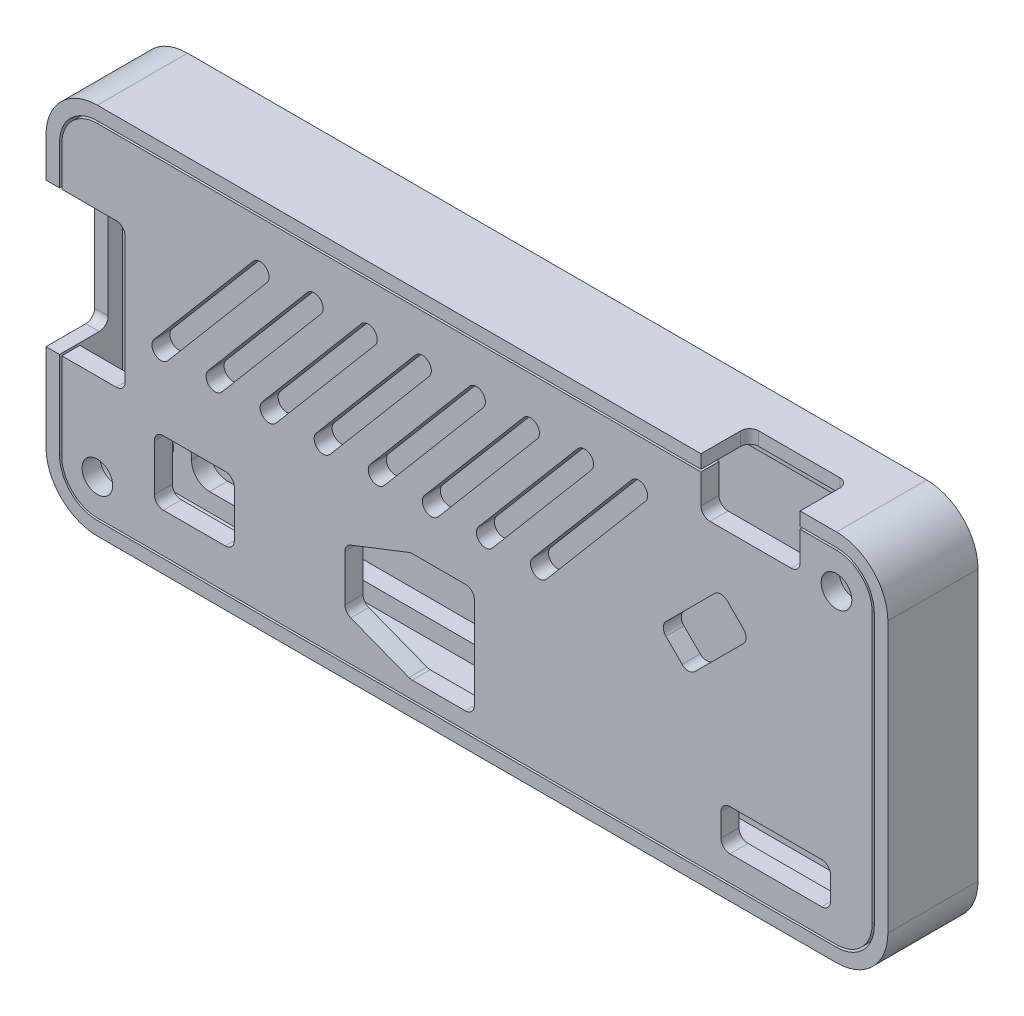
SolidWorks part; units mm, degrees
ref_plane "Front" through (0, 0, 0) normal (0, 0, 1) x (1, 0, 0)
ref_plane "Top" through (0, 0, 0) normal (0, 1, 0) x (1, 0, 0)
ref_plane "Right" through (0, 0, 0) normal (1, 0, 0) x (0, 0, -1)
sketch "Sketch1" plane through (0, 0, 0) normal (0, 0, 1) x (1, 0, 0)
  line L0 (-0.2, 4) -> (-0.2, 34)
  line L1 (4, 0) -> (86, 0) construction
  line L2 (0, 4) -> (0, 34) construction
  line L3 (4, 38) -> (86, 38) construction
  line L4 (90, 4) -> (90, 34) construction
  line L5 (4, 38.2) -> (86, 38.2)
  line L6 (90.2, 4) -> (90.2, 34)
  line L7 (4, -0.2) -> (86, -0.2)
  line L8 (4, 39.7) -> (86, 39.7)
  line L9 (91.7, 4) -> (91.7, 34)
  line L10 (4, -1.7) -> (86, -1.7)
  line L11 (-1.7, 4) -> (-1.7, 34)
  arc A0 (86, 38) -> (90, 34) centre (86, 34) cw construction
  arc A1 (86, 0) -> (90, 4) centre (86, 4) ccw construction
  arc A2 (4, 0) -> (0, 4) centre (4, 4) cw construction
  arc A3 (0, 34) -> (4, 38) centre (4, 34) cw construction
  arc A4 (-0.2, 34) -> (4, 38.2) centre (4, 34) cw
  arc A5 (86, 38.2) -> (90.2, 34) centre (86, 34) cw
  arc A6 (86, -0.2) -> (90.2, 4) centre (86, 4) ccw
  arc A7 (4, -0.2) -> (-0.2, 4) centre (4, 4) cw
  arc A8 (-1.7, 34) -> (4, 39.7) centre (4, 34) cw
  arc A9 (86, 39.7) -> (91.7, 34) centre (86, 34) cw
  arc A10 (86, -1.7) -> (91.7, 4) centre (86, 4) ccw
  arc A11 (4, -1.7) -> (-1.7, 4) centre (4, 4) cw
  point P9 (90, 0)
  point P12 (0, 0)
  point P15 (0, 38)
  dimension "D3" = 4
  dimension "D1" = 38
  dimension "D2" = 90
  dimension "D4" = 0.2
  dimension "D5" = 1.5
extrude "Boss-Extrude1" add sketch "Sketch1" against normal blind 3 contours L8 A9 L9 A10 L10 A11 L11 A8
extrude "Boss-Extrude2" add sketch "Sketch1<3>" along normal blind 7
sketch "Sketch1<3>" plane through (0, 0, 0) normal (0, 0, 1) x (1, 0, 0) same geometry as "Sketch1"
hole_wizard "M3x0.5 Tapped Hole1" positions "Sketch2" profile "Sketch3" tap size "M3x0.5" standard "ANSI Metric" end condition through all
sketch "Sketch2" plane through (0, 0, 0) normal (0, 0, 1) x (1, 0, 0)
  point P0 (4, 34)
  point P3 (4, 4)
  point P6 (86, 4)
  point P9 (86, 34)
sketch "Sketch3" plane through (4, 34, 0) normal (1, 0, 0) x (0, -1, 0)
  line L0 (0, 0) -> (0, 3)
  line L1 (0, 3) -> (1.45, 3)
  line L2 (1.45, 3) -> (1.45, 0)
  line L5 (1.45, 0) -> (0, 0)
  line L11 (0, -6.35) -> (0, 107.95) construction
  dimension "Thru Tap Drill Dia." = 2.9
  dimension "Thru Tap Drill Depth" = 3
cosmetic thread "Hole Thread1" parameters "D2"=3
cosmetic thread "Hole Thread2" parameters "D2"=3
cosmetic thread "Hole Thread3" parameters "D2"=3
cosmetic thread "Hole Thread4" parameters "D2"=3
sketch "Sketch4" plane through (0, 0, 0) normal (0, 0, 1) x (1, 0, 0)
  line L9 (1.8, 34) -> (1.8, 4)
  line L10 (86, 36.2) -> (4, 36.2)
  line L11 (88.2, 4) -> (88.2, 34)
  line L12 (4, 1.8) -> (86, 1.8)
  line L13 (1.8, 31.3425) -> (1.8, 6.6575)
  line L14 (83.3425, 36.2) -> (6.6575, 36.2)
  line L15 (88.2, 6.6575) -> (88.2, 31.3425)
  line L16 (6.6575, 1.8) -> (83.3425, 1.8)
  arc A6 (1.8, 31.3425) -> (6.6575, 36.2) centre (4, 34) ccw
  arc A15 (6.6575, 1.8) -> (1.8, 6.6575) centre (4, 4) ccw
  arc A16 (88.2, 6.6575) -> (83.3425, 1.8) centre (86, 4) ccw
  arc A17 (83.3425, 36.2) -> (88.2, 31.3425) centre (86, 34) ccw
  arc A26 (4, 36.2) -> (1.8, 34) centre (4, 34) ccw
  arc A27 (88.2, 34) -> (86, 36.2) centre (86, 34) ccw
  arc A28 (86, 1.8) -> (88.2, 4) centre (86, 4) ccw
  arc A29 (1.8, 4) -> (4, 1.8) centre (4, 4) ccw
  dimension "D1" = 3.45
  dimension "D6" = 2
extrude "Cut-Extrude1" cut sketch "Sketch4" against normal blind 2
fillet "Fillet1" radius 2 8 edges at (88.2, 31.3425, -1) (83.3425, 36.2, -1) (1.8, 31.3425, -1) (1.8, 6.6575, -1) (6.6575, 1.8, -1) (83.3425, 1.8, -1) (88.2, 6.6575, -1) (6.6575, 36.2, -1)
sketch "Sketch5" plane through (0, 0, 7) normal (0, 0, 1) x (1, 0, 0)
  line L1 (86, 37.95) -> (4, 37.95)
  line L2 (0.05, 34) -> (0.05, 4)
  line L3 (4, 0.05) -> (86, 0.05)
  line L4 (89.95, 4) -> (89.95, 34)
  line L5 (-0.2, 34) -> (-0.2, 4)
  line L6 (86, 38.2) -> (4, 38.2)
  line L7 (90.2, 4) -> (90.2, 34)
  line L8 (4, -0.2) -> (86, -0.2)
  line L9 (-0.2, 34) -> (-0.2, 4) construction
  line L10 (86, 38.2) -> (4, 38.2) construction
  line L11 (90.2, 4) -> (90.2, 34) construction
  line L12 (4, -0.2) -> (86, -0.2) construction
  arc A0 (4, 37.95) -> (0.05, 34) centre (4, 34) ccw
  arc A1 (0.05, 4) -> (4, 0.05) centre (4, 4) ccw
  arc A2 (86, 0.05) -> (89.95, 4) centre (86, 4) ccw
  arc A3 (89.95, 34) -> (86, 37.95) centre (86, 34) ccw
  arc A4 (-0.2, 4) -> (4, -0.2) centre (4, 4) ccw
  arc A5 (4, 38.2) -> (-0.2, 34) centre (4, 34) ccw
  arc A6 (90.2, 34) -> (86, 38.2) centre (86, 34) ccw
  arc A7 (86, -0.2) -> (90.2, 4) centre (86, 4) ccw
  arc A8 (-0.2, 4) -> (4, -0.2) centre (4, 4) ccw construction
  arc A9 (4, 38.2) -> (-0.2, 34) centre (4, 34) ccw construction
  arc A10 (90.2, 34) -> (86, 38.2) centre (86, 34) ccw construction
  arc A11 (86, -0.2) -> (90.2, 4) centre (86, 4) ccw construction
  dimension "D1" = 0
  dimension "D2" = 0.25
extrude "Boss-Extrude3" add sketch "Sketch5" against normal blind 2 separate body
sketch "Sketch6" plane through (0, 0, 7) normal (0, 0, 1) x (1, 0, 0)
  line L0 (38.7456, 14.0852) -> (31.4652, 11.2392) construction
  line L1 (45.8256, 14.0852) -> (38.7456, 14.0852) construction
  line L2 (45.8256, 1.9252) -> (45.8256, 14.0852) construction
  line L3 (38.7456, 1.9252) -> (45.8256, 1.9252) construction
  line L4 (31.4652, 4.7392) -> (38.7456, 1.9252) construction
  line L5 (31.4652, 11.2392) -> (31.4652, 4.7392) construction
  line L6 (-1.7, 29.6504) -> (7.082, 29.6504) construction
  line L7 (7.082, 13.6504) -> (-1.7, 13.6504) construction
  line L8 (7.082, 29.6504) -> (7.082, 13.6504) construction
  line L9 (19.1904, 11.6088) -> (19.1904, 4.4492) construction
  line L10 (10.3164, 11.6088) -> (10.3164, 4.4492) construction
  line L11 (10.3164, 4.4492) -> (19.1904, 4.4492) construction
  line L12 (10.3164, 11.6088) -> (19.1904, 11.6088) construction
  line L13 (81.967, 39.7) -> (81.967, 33.7) construction
  line L14 (70.967, 33.7) -> (81.967, 33.7) construction
  line L15 (70.967, 39.7) -> (70.967, 33.7) construction
  line L16 (69.5819, 17.7149) -> (66.3717, 20.9251) construction
  line L17 (66.3717, 20.9251) -> (73.1741, 27.7275) construction
  line L18 (73.1741, 27.7275) -> (76.3843, 24.5173) construction
  line L19 (76.3843, 24.5173) -> (69.5819, 17.7149) construction
  line L20 (73.188, 7.405) -> (73.188, 2.865) construction
  line L21 (73.188, 2.865) -> (85.348, 2.865) construction
  line L22 (85.348, 7.405) -> (85.348, 2.865) construction
  line L23 (73.188, 7.405) -> (85.348, 7.405) construction
  line L24 (38.7456, 14.0852) -> (31.4652, 11.2392)
  line L25 (45.8256, 14.0852) -> (38.7456, 14.0852)
  line L26 (45.8256, 1.9252) -> (45.8256, 14.0852)
  line L27 (38.7456, 1.9252) -> (45.8256, 1.9252)
  line L28 (31.4652, 4.7392) -> (38.7456, 1.9252)
  line L29 (31.4652, 11.2392) -> (31.4652, 4.7392)
  line L30 (-1.7, 29.6504) -> (7.082, 29.6504)
  line L31 (7.082, 13.6504) -> (-1.7, 13.6504)
  line L32 (7.082, 29.6504) -> (7.082, 13.6504)
  line L33 (19.1904, 11.6088) -> (19.1904, 4.4492)
  line L34 (10.3164, 11.6088) -> (10.3164, 4.4492)
  line L35 (10.3164, 4.4492) -> (19.1904, 4.4492)
  line L36 (10.3164, 11.6088) -> (19.1904, 11.6088)
  line L37 (81.967, 39.7) -> (81.967, 33.7)
  line L38 (70.967, 33.7) -> (81.967, 33.7)
  line L39 (70.967, 39.7) -> (70.967, 33.7)
  line L40 (69.5819, 17.7149) -> (66.3717, 20.9251)
  line L41 (66.3717, 20.9251) -> (73.1741, 27.7275)
  line L42 (73.1741, 27.7275) -> (76.3843, 24.5173)
  line L43 (76.3843, 24.5173) -> (69.5819, 17.7149)
  line L44 (73.188, 7.405) -> (73.188, 2.865)
  line L45 (73.188, 2.865) -> (85.348, 2.865)
  line L46 (85.348, 7.405) -> (85.348, 2.865)
  line L47 (73.188, 7.405) -> (85.348, 7.405)
  line L48 (-1.7, 29.6504) -> (-1.7, 13.6504)
  line L49 (70.967, 39.7) -> (81.967, 39.7)
extrude "Cut-Extrude2" cut sketch "Sketch6" against normal offset from surface (5.4 mm away) 1.6 up to face at (45, 19, 0)
fillet "Fillet2" radius 1 22 edges at (73.188, 2.865, 6) (85.348, 2.865, 6) (85.348, 7.405, 6) (73.188, 7.405, 6) (73.1741, 27.7275, 6) (66.3717, 20.9251, 6) (69.5819, 17.7149, 6) (76.3843, 24.5173, 6) (70.967, 33.7, 6) (81.967, 33.7, 6) (10.3164, 4.4492, 6) (19.1904, 4.4492, 6) (19.1904, 11.6088, 6) (10.3164, 11.6088, 6) (7.082, 13.6504, 6) (31.4652, 11.2392, 6) (31.4652, 4.7392, 6) (38.7456, 1.9252, 6) (45.8256, 1.9252, 6) (45.8256, 14.0852, 6) (38.7456, 14.0852, 6) (7.082, 29.6504, 6)
sketch "Sketch7" plane through (0, 0, 7) normal (0, 0, 1) x (1, 0, 0)
  line L0 (11.05, 19.7) -> (22.05, 32.7) construction
  line L1 (10.2866, 20.3459) -> (21.2866, 33.3459)
  line L2 (11.8134, 19.0541) -> (22.8134, 32.0541)
  line L3 (17.05, 19.7) -> (28.05, 32.7) construction
  line L4 (16.2866, 20.3459) -> (27.2866, 33.3459)
  line L5 (17.8134, 19.0541) -> (28.8134, 32.0541)
  line L6 (23.05, 19.7) -> (34.05, 32.7) construction
  line L7 (22.2866, 20.3459) -> (33.2866, 33.3459)
  line L8 (23.8134, 19.0541) -> (34.8134, 32.0541)
  line L9 (29.05, 19.7) -> (40.05, 32.7) construction
  line L10 (28.2866, 20.3459) -> (39.2866, 33.3459)
  line L11 (29.8134, 19.0541) -> (40.8134, 32.0541)
  line L12 (35.05, 19.7) -> (46.05, 32.7) construction
  line L13 (34.2866, 20.3459) -> (45.2866, 33.3459)
  line L14 (35.8134, 19.0541) -> (46.8134, 32.0541)
  line L15 (41.05, 19.7) -> (52.05, 32.7) construction
  line L16 (40.2866, 20.3459) -> (51.2866, 33.3459)
  line L17 (41.8134, 19.0541) -> (52.8134, 32.0541)
  line L18 (47.05, 19.7) -> (58.05, 32.7) construction
  line L19 (46.2866, 20.3459) -> (57.2866, 33.3459)
  line L20 (47.8134, 19.0541) -> (58.8134, 32.0541)
  line L21 (53.05, 19.7) -> (64.05, 32.7) construction
  line L22 (52.2866, 20.3459) -> (63.2866, 33.3459)
  line L23 (53.8134, 19.0541) -> (64.8134, 32.0541)
  line L24 (4, 39.7) -> (86, 39.7) construction
  arc A0 (10.2866, 20.3459) -> (11.8134, 19.0541) centre (11.05, 19.7) ccw
  arc A1 (22.8134, 32.0541) -> (21.2866, 33.3459) centre (22.05, 32.7) ccw
  arc A2 (16.2866, 20.3459) -> (17.8134, 19.0541) centre (17.05, 19.7) ccw
  arc A3 (28.8134, 32.0541) -> (27.2866, 33.3459) centre (28.05, 32.7) ccw
  arc A4 (22.2866, 20.3459) -> (23.8134, 19.0541) centre (23.05, 19.7) ccw
  arc A5 (34.8134, 32.0541) -> (33.2866, 33.3459) centre (34.05, 32.7) ccw
  arc A6 (28.2866, 20.3459) -> (29.8134, 19.0541) centre (29.05, 19.7) ccw
  arc A7 (40.8134, 32.0541) -> (39.2866, 33.3459) centre (40.05, 32.7) ccw
  arc A8 (34.2866, 20.3459) -> (35.8134, 19.0541) centre (35.05, 19.7) ccw
  arc A9 (46.8134, 32.0541) -> (45.2866, 33.3459) centre (46.05, 32.7) ccw
  arc A10 (40.2866, 20.3459) -> (41.8134, 19.0541) centre (41.05, 19.7) ccw
  arc A11 (52.8134, 32.0541) -> (51.2866, 33.3459) centre (52.05, 32.7) ccw
  arc A12 (46.2866, 20.3459) -> (47.8134, 19.0541) centre (47.05, 19.7) ccw
  arc A13 (58.8134, 32.0541) -> (57.2866, 33.3459) centre (58.05, 32.7) ccw
  arc A14 (52.2866, 20.3459) -> (53.8134, 19.0541) centre (53.05, 19.7) ccw
  arc A15 (64.8134, 32.0541) -> (63.2866, 33.3459) centre (64.05, 32.7) ccw
  point P2 (16.55, 26.2)
  point P10 (22.55, 26.2)
  point P17 (28.55, 26.2)
  point P24 (34.55, 26.2)
  point P31 (40.55, 26.2)
  point P38 (46.55, 26.2)
  point P45 (52.55, 26.2)
  point P52 (58.55, 26.2)
  dimension "D1" = 8
  dimension "D2" = 2
  dimension "D3" = 13
  dimension "D4" = 11
  dimension "D5" = 11
  dimension "D6" = 7
  dimension "D7" = 6
extrude "Cut-Extrude3" cut sketch "Sketch7" against normal up to surface (2 mm away) up to face at (38.6305, 8.0001, 5)
sketch "Sketch8" plane through (0, 0, 7) normal (0, 0, 1) x (1, 0, 0)
  circle A0 centre (4, 4) radius 1.7
  circle A1 centre (86, 34) radius 1.7
  dimension "D1" = 3.4
  dimension "D2" = 3.4
extrude "Cut-Extrude4" cut sketch "Sketch8" against normal through all
fillet "Fillet3" radius 1 4 edges at (70.967, 38.95, 1.6) (81.967, 38.95, 1.6) (-0.95, 13.6504, 1.6) (-0.95, 29.6504, 1.6)
